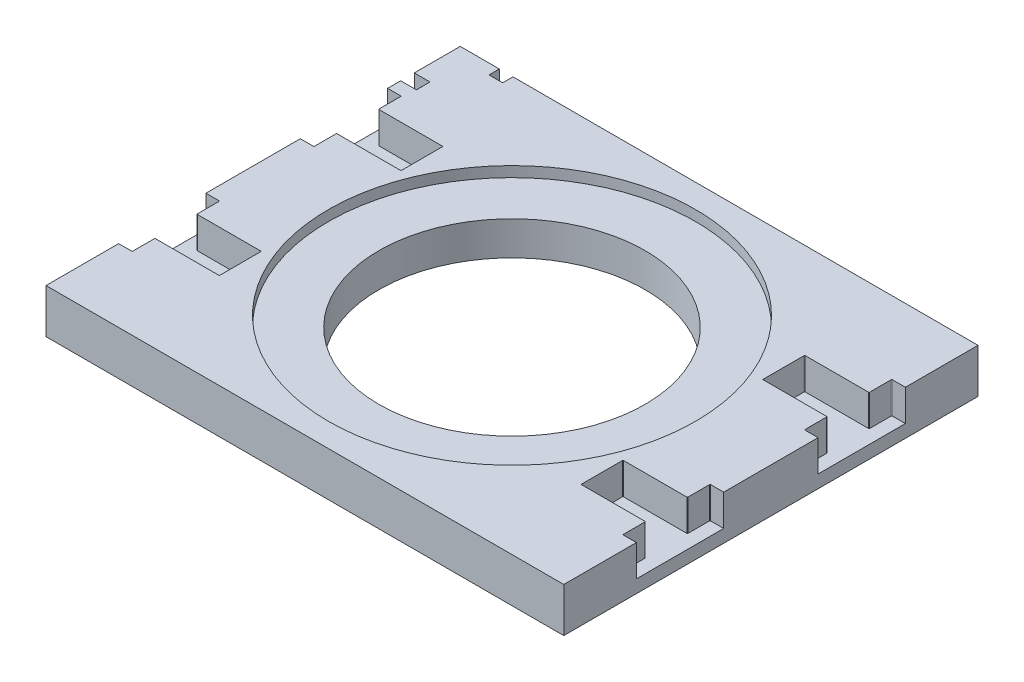
SolidWorks part; units mm, degrees
ref_plane "Front Plane" through (0, 0, 0) normal (0, 0, 1) x (1, 0, 0)
ref_plane "Top Plane" through (0, 0, 0) normal (0, 1, 0) x (1, 0, 0)
ref_plane "Right Plane" through (0, 0, 0) normal (1, 0, 0) x (0, 0, -1)
sketch "Sketch2" plane through (0, 0, 0) normal (0, 1, 0) x (1, 0, 0)
  line L0 (-125.4125, 65.151) -> (-119.0752, 65.151)
  line L1 (-125.4125, -100.33) -> (125.4125, -100.33)
  line L2 (-125.4125, -100.33) -> (-125.4125, -65.151)
  line L3 (-125.4125, 100.33) -> (125.4125, 100.33)
  line L4 (125.4125, -100.33) -> (125.4125, -65.151)
  line L5 (-125.4125, -100.33) -> (125.4125, 100.33) construction
  line L6 (-125.4125, 100.33) -> (125.4125, -100.33) construction
  line L7 (-118.8212, 64.897) -> (-118.8212, 54.4195)
  line L8 (-118.5672, 54.1655) -> (-87.8713, 54.1655)
  line L9 (-87.6173, 53.9115) -> (-87.6173, 34.0995)
  line L10 (-87.8713, 33.8455) -> (-118.5672, 33.8455)
  line L11 (-118.8212, 33.5915) -> (-118.8212, 23.114)
  line L12 (-119.0752, 22.86) -> (-125.4125, 22.86)
  line L15 (0, -55) -> (0, 55) construction
  line L16 (119.0752, 22.86) -> (125.4125, 22.86)
  line L17 (118.8212, 33.5915) -> (118.8212, 23.114)
  line L18 (87.8713, 33.8455) -> (118.5672, 33.8455)
  line L19 (87.6173, 53.9115) -> (87.6173, 34.0995)
  line L20 (118.5672, 54.1655) -> (87.8713, 54.1655)
  line L21 (118.8212, 64.897) -> (118.8212, 54.4195)
  line L22 (125.4125, 65.151) -> (119.0752, 65.151)
  line L24 (-55, 0) -> (55, 0) construction
  line L25 (118.8212, -33.5915) -> (118.8212, -23.114)
  line L26 (87.8713, -33.8455) -> (118.5672, -33.8455)
  line L27 (87.6173, -53.9115) -> (87.6173, -34.0995)
  line L28 (118.5672, -54.1655) -> (87.8713, -54.1655)
  line L29 (118.8212, -64.897) -> (118.8212, -54.4195)
  line L30 (125.4125, -65.151) -> (119.0752, -65.151)
  line L32 (119.0752, -22.86) -> (125.4125, -22.86)
  line L33 (-119.0752, -22.86) -> (-125.4125, -22.86)
  line L34 (-118.8212, -33.5915) -> (-118.8212, -23.114)
  line L35 (-87.8713, -33.8455) -> (-118.5672, -33.8455)
  line L36 (-87.6173, -53.9115) -> (-87.6173, -34.0995)
  line L37 (-118.5672, -54.1655) -> (-87.8713, -54.1655)
  line L38 (-118.8212, -64.897) -> (-118.8212, -54.4195)
  line L39 (-125.4125, -65.151) -> (-119.0752, -65.151)
  line L42 (-125.4125, -22.86) -> (-125.4125, 22.86)
  line L43 (125.4125, 65.151) -> (125.4125, 100.33)
  line L44 (125.4125, -22.86) -> (125.4125, 22.86)
  line L49 (-125.4125, 100.33) -> (-125.4125, 65.151)
  arc A0 (-118.5672, 33.8455) -> (-118.8212, 33.5915) centre (-118.5672, 33.5915) ccw
  arc A1 (-118.8212, 54.4195) -> (-118.5672, 54.1655) centre (-118.5672, 54.4195) ccw
  arc A2 (-87.6173, 34.0995) -> (-87.8713, 33.8455) centre (-87.8713, 34.0995) cw
  arc A3 (-87.8713, 54.1655) -> (-87.6173, 53.9115) centre (-87.8713, 53.9115) cw
  arc A4 (-118.8212, 23.114) -> (-119.0752, 22.86) centre (-119.0752, 23.114) cw
  arc A5 (-119.0752, 65.151) -> (-118.8212, 64.897) centre (-119.0752, 64.897) cw
  arc A6 (118.8212, 23.114) -> (119.0752, 22.86) centre (119.0752, 23.114) ccw
  arc A7 (118.5672, 33.8455) -> (118.8212, 33.5915) centre (118.5672, 33.5915) cw
  arc A8 (87.6173, 34.0995) -> (87.8713, 33.8455) centre (87.8713, 34.0995) ccw
  arc A9 (87.8713, 54.1655) -> (87.6173, 53.9115) centre (87.8713, 53.9115) ccw
  arc A10 (118.8212, 54.4195) -> (118.5672, 54.1655) centre (118.5672, 54.4195) cw
  arc A11 (119.0752, 65.151) -> (118.8212, 64.897) centre (119.0752, 64.897) ccw
  arc A12 (118.8212, -23.114) -> (119.0752, -22.86) centre (119.0752, -23.114) cw
  arc A13 (118.5672, -33.8455) -> (118.8212, -33.5915) centre (118.5672, -33.5915) ccw
  arc A14 (87.6173, -34.0995) -> (87.8713, -33.8455) centre (87.8713, -34.0995) cw
  arc A15 (87.8713, -54.1655) -> (87.6173, -53.9115) centre (87.8713, -53.9115) cw
  arc A16 (118.8212, -54.4195) -> (118.5672, -54.1655) centre (118.5672, -54.4195) ccw
  arc A17 (119.0752, -65.151) -> (118.8212, -64.897) centre (119.0752, -64.897) cw
  arc A18 (-118.8212, -23.114) -> (-119.0752, -22.86) centre (-119.0752, -23.114) ccw
  arc A19 (-118.5672, -33.8455) -> (-118.8212, -33.5915) centre (-118.5672, -33.5915) cw
  arc A20 (-87.6173, -34.0995) -> (-87.8713, -33.8455) centre (-87.8713, -34.0995) ccw
  arc A21 (-87.8713, -54.1655) -> (-87.6173, -53.9115) centre (-87.8713, -53.9115) ccw
  arc A22 (-118.8212, -54.4195) -> (-118.5672, -54.1655) centre (-118.5672, -54.4195) cw
  arc A23 (-119.0752, -65.151) -> (-118.8212, -64.897) centre (-119.0752, -64.897) ccw
  point P0 (0, 0)
  point P23 (-87.6173, 33.8455)
  point P26 (-87.6173, 54.1655)
  point P29 (-118.8212, 22.86)
  dimension "D8" = 0.254
  dimension "D9" = 0.254
  dimension "D10" = 35.179
  dimension "D1" = 250.825
  dimension "D2" = 200.66
  dimension "D3" = 67.691
  dimension "D4" = 19.812
  dimension "D5" = 6.3373
  dimension "D6" = 37.7952
  dimension "D7" = 6.3373
  dimension "D11" = 6.3373
extrude "Boss-Extrude1" add sketch "Sketch2" along normal blind 21.463
sketch "Sketch3" plane through (0, 21.463, 0) normal (0, 1, 0) x (1, 0, 0)
  circle A0 centre (0, 0) radius 88.9
  dimension "D1" = 177.8
extrude "Cut-Extrude1" cut sketch "Sketch3" against normal blind 5.0546
sketch "Sketch4" plane through (0, 16.4084, 0) normal (0, 1, 0) x (1, 0, 0)
  circle A0 centre (0, 0) radius 64.5033
  dimension "D1" = 129.0066
extrude "Cut-Extrude2" cut sketch "Sketch4" against normal through all and the other way through all
sketch "Sketch5" plane through (0, 0, 0) normal (0, -1, 0) x (1, 0, 0)
  line L1 (-125.4125, 100.33) -> (125.4125, 100.33)
  line L2 (-125.4125, 100.33) -> (-125.4125, -100.33)
  line L3 (-125.4125, -100.33) -> (125.4125, -100.33)
  line L4 (125.4125, 100.33) -> (125.4125, -100.33)
extrude "Boss-Extrude2" add sketch "Sketch5" against normal blind 6.223
extrude "Cut-Extrude3" cut sketch "Sketch4<2>" against normal through all both and the other way through all
sketch "Sketch4<2>" plane through (0, 16.4084, 0) normal (0, 1, 0) x (1, 0, 0) same geometry as "Sketch4"
sketch "Sketch6" plane through (0, 21.463, 0) normal (0, 1, 0) x (1, 0, 0)
  line L0 (125.4125, 100.33) -> (-125.4125, 100.33) construction
  line L1 (-106.4641, 100.33) -> (-99.8601, 100.33)
  line L2 (-106.4641, 100.33) -> (-106.4641, 95.3262)
  line L3 (-106.4641, 95.3262) -> (-99.8601, 95.3262)
  line L4 (-99.8601, 100.33) -> (-99.8601, 95.3262)
  line L5 (-125.4125, 100.33) -> (-125.4125, 65.151) construction
  line L11 (-125.4125, 78.0796) -> (-117.7925, 78.0796)
  line L12 (-125.4125, 78.0796) -> (-125.4125, 71.4756)
  line L13 (-125.4125, 71.4756) -> (-117.7925, 71.4756)
  line L14 (-117.7925, 78.0796) -> (-117.7925, 71.4756)
  dimension "D1" = 6.604
  dimension "D2" = 6.604
  dimension "D3" = 18.9484
  dimension "D4" = 5.0038
  dimension "D5" = 22.2504
  dimension "D6" = 7.62
ref_plane "Plane1" through (0, 16.891, 0) normal (0, 1, 0) x (1, 0, 0)
sketch "Sketch7" plane through (0, 16.891, 0) normal (0, 1, 0) x (1, 0, 0)
  line L1 (-106.4641, 100.33) -> (-99.8601, 100.33)
  line L2 (-106.4641, 100.33) -> (-106.4641, 95.3262)
  line L3 (-106.4641, 95.3262) -> (-99.8601, 95.3262)
  line L4 (-99.8601, 100.33) -> (-99.8601, 95.3262)
  line L5 (-125.4125, 78.0796) -> (-117.7925, 78.0796)
  line L6 (-125.4125, 78.0796) -> (-125.4125, 71.4756)
  line L7 (-125.4125, 71.4756) -> (-117.7925, 71.4756)
  line L8 (-117.7925, 78.0796) -> (-117.7925, 71.4756)
extrude "Cut-Extrude4" cut sketch "Sketch6" against normal blind 11.176
fillet "Fillet4" radius 1.27 4 edges at (-121.6025, 10.287, -78.0796) (-121.6025, 10.287, -71.4756) (-99.8601, 10.287, -97.8281) (-106.4641, 10.287, -97.8281)
sketch "Sketch8" plane through (0, 0, 0) normal (0, -1, 0) x (1, 0, 0)
  line L1 (-125.4125, 100.33) -> (125.4125, 100.33)
  line L2 (-125.4125, 100.33) -> (-125.4125, -100.33)
  line L3 (-125.4125, -100.33) -> (125.4125, -100.33)
  line L4 (125.4125, 100.33) -> (125.4125, -100.33)
equation "\"0.100.0in\"=0.1"
